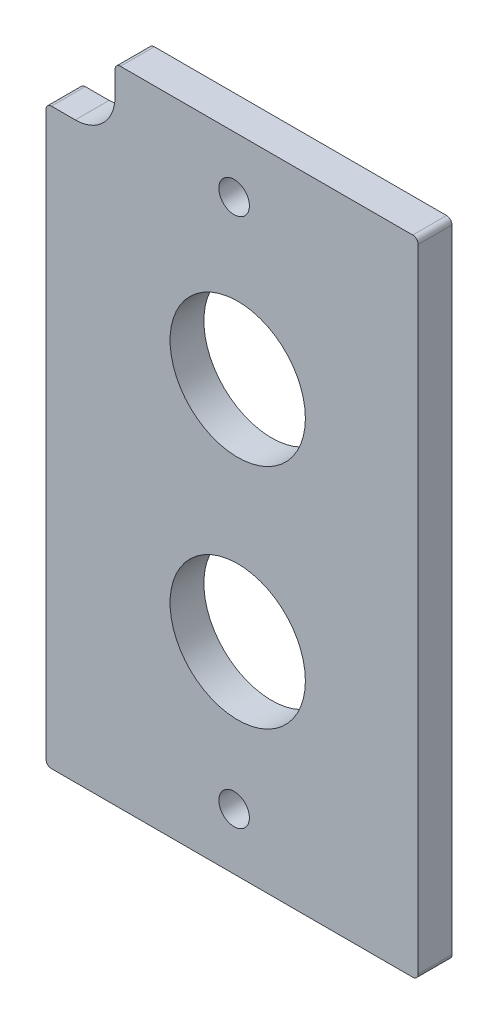
SolidWorks part; units mm, degrees
material "Acrylic (Medium-high impact)"
ref_plane "Front Plane" through (0, 0, 0) normal (0, 0, 1) x (1, 0, 0)
ref_plane "Top Plane" through (0, 0, 0) normal (0, 1, 0) x (1, 0, 0)
ref_plane "Right Plane" through (0, 0, 0) normal (1, 0, 0) x (0, 0, -1)
sketch "Sketch1" plane through (0, 0, 0) normal (0, 0, 1) x (1, 0, 0)
  line L6 (-50.8, 124.587) -> (-54.1655, 124.587)
  line L7 (-54.9275, 123.825) -> (-54.9275, 44.577)
  line L8 (-54.1655, 43.815) -> (-3.302, 43.815)
  line L9 (-2.54, 44.577) -> (-2.54, 133.5405)
  line L10 (-3.302, 134.3025) -> (-44.45, 134.3025)
  line L11 (-45.212, 133.5405) -> (-45.212, 130.175)
  line L12 (-50.8, 124.587) -> (-54.1655, 124.587)
  line L13 (-54.9275, 123.825) -> (-54.9275, 44.577)
  line L14 (-54.1655, 43.815) -> (-3.302, 43.815)
  line L15 (-2.54, 44.577) -> (-2.54, 133.5405)
  line L16 (-3.302, 134.3025) -> (-44.45, 134.3025)
  line L17 (-45.212, 133.5405) -> (-45.212, 130.175)
  arc A6 (-50.8, 124.587) -> (-45.212, 130.175) centre (-50.8, 130.175) ccw
  arc A7 (-54.1655, 124.587) -> (-54.9275, 123.825) centre (-54.1655, 123.825) ccw
  arc A8 (-54.9275, 44.577) -> (-54.1655, 43.815) centre (-54.1655, 44.577) ccw
  arc A9 (-3.302, 43.815) -> (-2.54, 44.577) centre (-3.302, 44.577) ccw
  arc A10 (-2.54, 133.5405) -> (-3.302, 134.3025) centre (-3.302, 133.5405) ccw
  arc A11 (-44.45, 134.3025) -> (-45.212, 133.5405) centre (-44.45, 133.5405) ccw
  arc A12 (-50.8, 124.587) -> (-45.212, 130.175) centre (-50.8, 130.175) ccw
  arc A13 (-54.1655, 124.587) -> (-54.9275, 123.825) centre (-54.1655, 123.825) ccw
  arc A14 (-54.9275, 44.577) -> (-54.1655, 43.815) centre (-54.1655, 44.577) ccw
  arc A15 (-3.302, 43.815) -> (-2.54, 44.577) centre (-3.302, 44.577) ccw
  arc A16 (-2.54, 133.5405) -> (-3.302, 134.3025) centre (-3.302, 133.5405) ccw
  arc A17 (-44.45, 134.3025) -> (-45.212, 133.5405) centre (-44.45, 133.5405) ccw
  dimension "D1" = 0
extrude "Boss-Extrude1" add sketch "Sketch1" along normal blind 4.7625
hole_wizard "#6 Clearance Hole1" positions "Sketch3" profile "Sketch2" hole size "#6" standard "ANSI Inch" end condition through all
sketch "Sketch3" plane through (0, 0, 4.7625) normal (0, 0, 1) x (1, 0, 0)
  point P0 (-28.448, 126.365)
  point P3 (-28.448, 51.7525)
sketch "Sketch2" plane through (-28.448, 126.365, 4.7625) normal (1, 0, 0) x (0, -1, 0)
  line L0 (0, 0) -> (0, 4.7625)
  line L1 (0, 4.7625) -> (2.1526, 4.7625)
  line L2 (2.1526, 4.7625) -> (2.1526, 0)
  line L5 (2.1526, 0) -> (0, 0)
  line L11 (0, -6.35) -> (0, 107.95) construction
  dimension "Thru Hole Dia." = 4.3053
  dimension "Thru Hole Depth" = 4.7625
hole_wizard "3/4 (0.75) Diameter Hole1" positions "Sketch5" profile "Sketch4" hole size "3/4" standard "ANSI Inch" end condition through all
sketch "Sketch5" plane through (0, 0, 4.7625) normal (0, 0, 1) x (1, 0, 0)
  point P0 (-27.94, 72.39)
  point P3 (-27.94, 104.394)
sketch "Sketch4" plane through (-27.94, 72.39, 4.7625) normal (1, 0, 0) x (0, -1, 0)
  line L0 (0, 0) -> (0, 4.7625)
  line L1 (0, 4.7625) -> (9.525, 4.7625)
  line L2 (9.525, 4.7625) -> (9.525, 0)
  line L5 (9.525, 0) -> (0, 0)
  line L11 (0, -6.35) -> (0, 107.95) construction
  dimension "Thru Hole Dia." = 19.05
  dimension "Thru Hole Depth" = 4.7625
